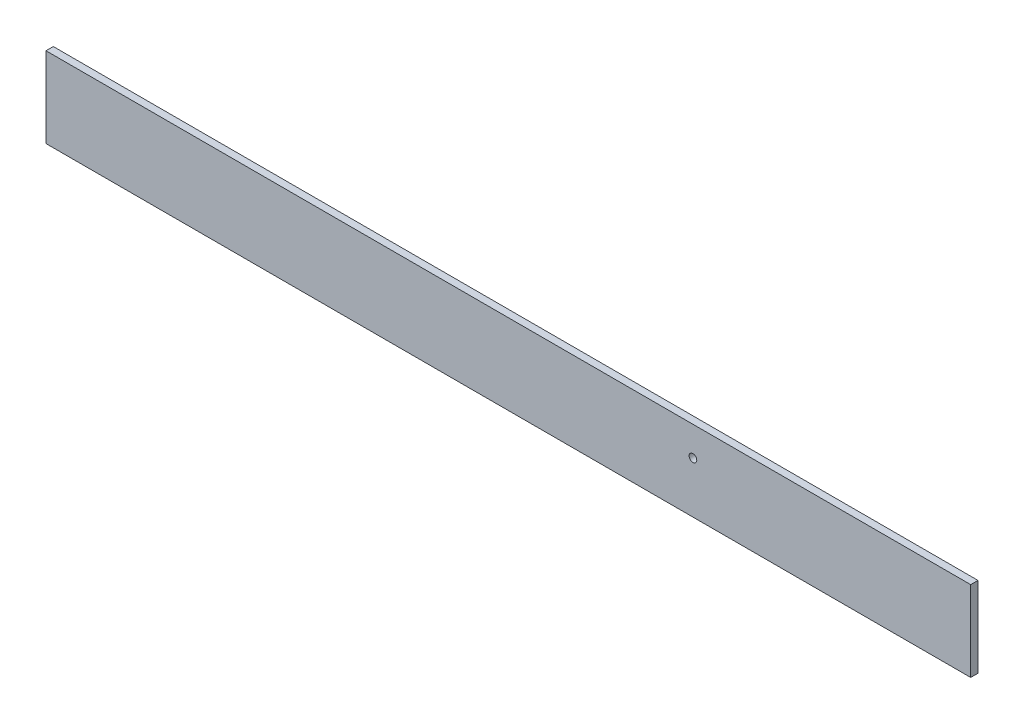
SolidWorks part; units mm, degrees
ref_plane "Front Plane" through (0, 0, 0) normal (0, 0, 1) x (1, 0, 0)
ref_plane "Top Plane" through (0, 0, 0) normal (0, 1, 0) x (1, 0, 0)
ref_plane "Right Plane" through (0, 0, 0) normal (1, 0, 0) x (0, 0, -1)
sketch "Sketch2" plane through (0, 0, 0) normal (0, 0, 1) x (1, 0, 0)
  line L1 (-253, -22) -> (253, -22)
  line L2 (-253, -22) -> (-253, 22)
  line L3 (-253, 22) -> (253, 22)
  line L4 (253, -22) -> (253, 22)
  line L5 (-253, -22) -> (253, 22) construction
  line L6 (-253, 22) -> (253, -22) construction
  circle A0 centre (101, 6) radius 2.1 construction
  circle A1 centre (101, 6) radius 2.1
  point P0 (0, 0)
  dimension "D1" = 44
  dimension "D2" = 506
extrude "Boss-Extrude1" add sketch "Sketch2" along normal blind 4
